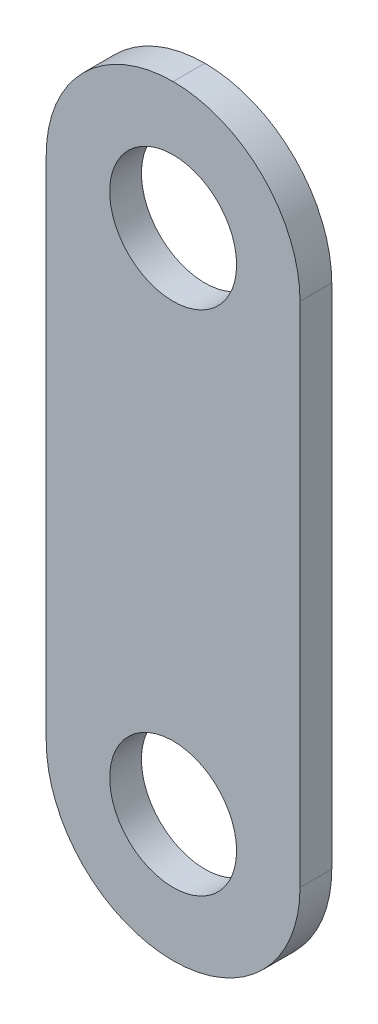
SolidWorks part; units mm, degrees
ref_plane "Front Plane" through (0, 0, 0) normal (0, 0, 1) x (1, 0, 0)
ref_plane "Top Plane" through (0, 0, 0) normal (0, 1, 0) x (1, 0, 0)
ref_plane "Right Plane" through (0, 0, 0) normal (1, 0, 0) x (0, 0, -1)
sketch "Sketch1" plane through (0, 0, 0) normal (0, 0, 1) x (1, 0, 0)
  line L1 (12.7, 0) -> (0, 0)
  line L3 (12.7, 38.1) -> (0, 38.1)
  line L4 (0, 0) -> (0, 38.1)
  line L7 (12.7, 38.1) -> (12.7, 0)
  line L8 (6.35, 38.1) -> (6.35, 0) construction
  circle A0 centre (6.35, 31.75) radius 3.175
  circle A1 centre (6.35, 6.35) radius 3.175
  point P4 (0, 0)
  point P5 (0, 0)
  point P6 (12.7, -0.4822)
  dimension "D1" = 6.35
  dimension "D2" = 6.35
  dimension "D3" = 12.7
  dimension "D4" = 25.4
  dimension "D5" = 6.35
extrude "Boss-Extrude1" add sketch "Sketch1" along normal blind 1.5875
fillet "Fillet1" radius 6.35 4 edges at (12.7, 38.1, 0.7937) (0, 38.1, 0.7937) (0, 0, 0.7937) (12.7, 0, 0.7937)
